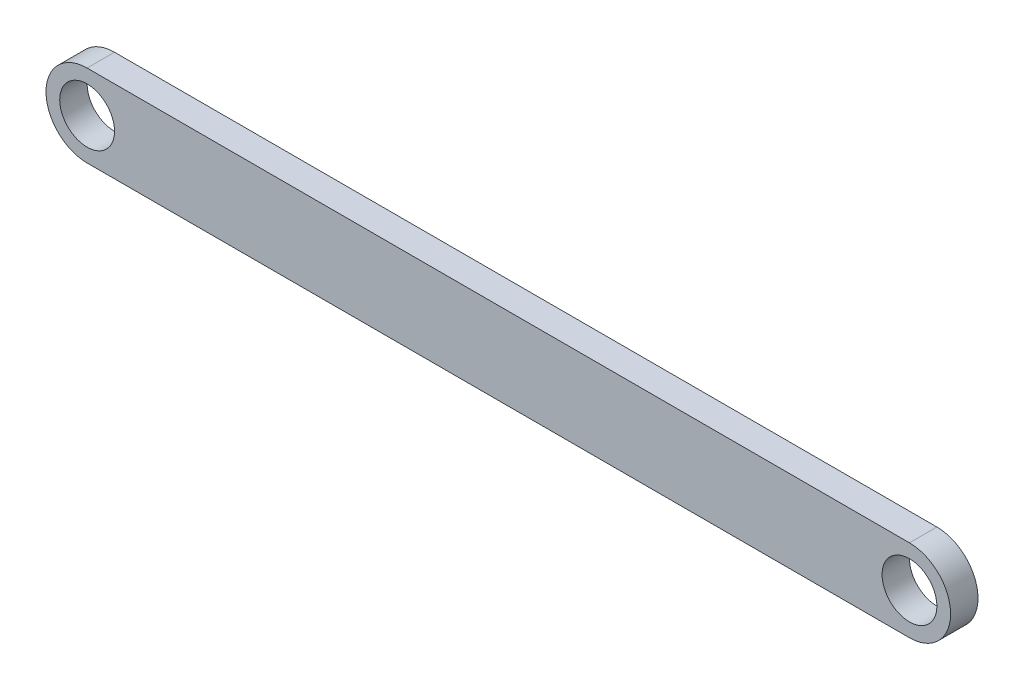
SolidWorks part; units mm, degrees
material "Acrylic (Medium-high impact)"
ref_plane "Front Plane" through (0, 0, 0) normal (0, 0, 1) x (1, 0, 0)
ref_plane "Top Plane" through (0, 0, 0) normal (0, 1, 0) x (1, 0, 0)
ref_plane "Right Plane" through (0, 0, 0) normal (1, 0, 0) x (0, 0, -1)
sketch "Sketch1" plane through (0, 0, 0) normal (0, 0, 1) x (1, 0, 0)
  line L0 (75, 0) -> (-75, 0) construction
  line L1 (75, -7.5) -> (-75, -7.5)
  line L2 (75, 7.5) -> (-75, 7.5)
  line L3 (0, 7.5) -> (0, -7.5) construction
  arc A0 (75, -7.5) -> (75, 7.5) centre (75, 0) ccw
  arc A1 (-75, 7.5) -> (-75, -7.5) centre (-75, 0) ccw
  circle A2 centre (75, 0) radius 5
  circle A3 centre (-75, 0) radius 5
  point P2 (0, 0)
  point P14 (19, 0)
  point P15 (-14, 0)
  point P16 (0, 3.5)
  point P17 (0, -3.5)
  point P30 (0, 3.5)
  point P33 (0, -3.5)
  dimension "D2" = 10
  dimension "D1" = 150
  dimension "D3" = 15
  dimension "D4" = 19
  dimension "D5" = 14
  dimension "D6" = 3.5
  dimension "D7" = 3.5
extrude "Boss-Extrude1" add sketch "Sketch1" along normal blind 5
